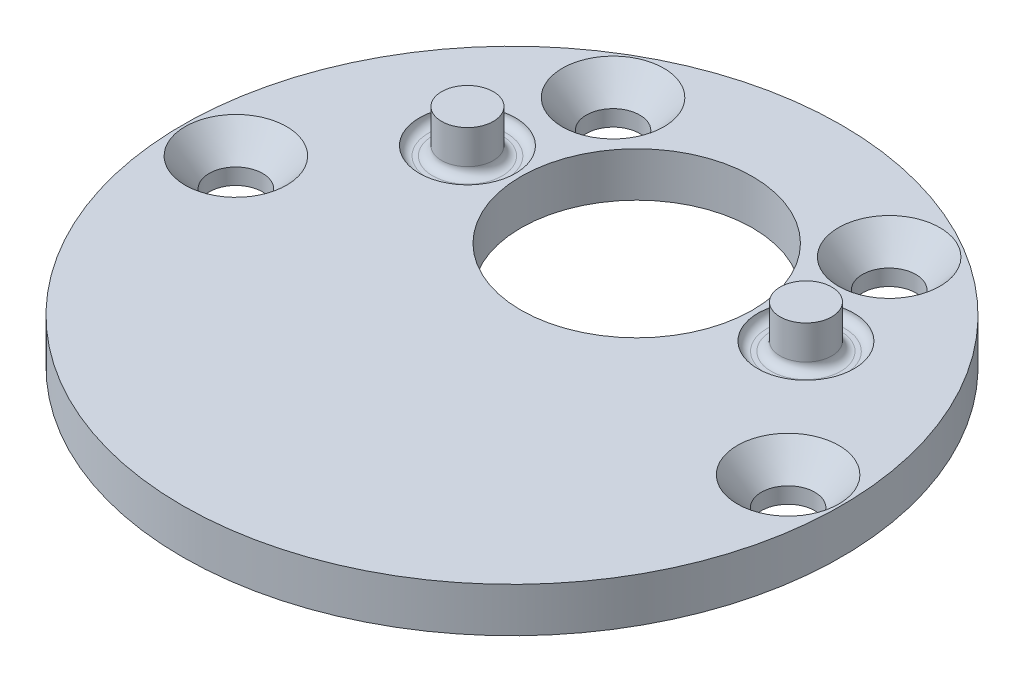
SolidWorks part; units mm, degrees
ref_plane "Front Plane" through (0, 0, 0) normal (0, 0, 1) x (1, 0, 0)
ref_plane "Top Plane" through (0, 0, 0) normal (0, 1, 0) x (1, 0, 0)
ref_plane "Right Plane" through (0, 0, 0) normal (1, 0, 0) x (0, 0, -1)
sketch "Sketch1" plane through (0, 0, 0) normal (0, 1, 0) x (1, 0, 0)
  line L4 (0, 0) -> (15.8817, 0) construction
  line L5 (0, 0) -> (0, 17.0912) construction
  line L6 (-7.75, 13.4234) -> (0, 0) construction
  line L7 (0, 0) -> (7.75, 13.4234) construction
  circle A0 centre (0, 0) radius 15.5 construction
  circle A1 centre (-7.75, 13.4234) radius 1.5
  circle A3 centre (-15.5, 0) radius 1.5
  circle A4 centre (7.75, 13.4234) radius 1.5
  circle A5 centre (15.5, 0) radius 1.5
  circle A6 centre (0, 0) radius 18.5
  dimension "D1" = 31
  dimension "D2" = 3
  dimension "D4" = 37
  dimension "D3" = 60
extrude "Boss-Extrude1" add sketch "Sketch1" along normal blind 2.5
sketch "Sketch2" plane through (0, 2.5, 0) normal (0, 1, 0) x (1, 0, 0)
  line L0 (0, 0) -> (0, 16.6144) construction
  line L1 (0, 0) -> (25.2906, 0) construction
  line L2 (-9.5, 7) -> (9.5, 7) construction
  circle A0 centre (-9.5, 7) radius 1.45
  circle A1 centre (9.5, 7) radius 1.45
  point P8 (0, 8.3072)
  point P11 (0, 7)
  dimension "D3" = 2.9
  dimension "D1" = 7
  dimension "D2" = 19
extrude "Boss-Extrude2" add sketch "Sketch2" along normal blind 1.9 and the other way blind 1
sketch "Sketch6" plane through (0, 2.5, 0) normal (0, 1, 0) x (1, 0, 0)
  line L0 (9.5, 7) -> (-9.5, 7) construction
  line L1 (0, 0) -> (0, 7) construction
  circle A0 centre (-9.5, 7) radius 2.7
  circle A1 centre (9.5, 7) radius 2.7
  circle A2 centre (-9.5, 7) radius 1.45 construction
  circle A3 centre (9.5, 7) radius 1.45
  circle A4 centre (-9.5, 7) radius 1.45
  circle A5 centre (9.5, 7) radius 1.45 construction
  dimension "D1" = 1.25
extrude "Cut-Extrude3" cut sketch "Sketch6" against normal blind 0.5
sketch "Sketch4" plane through (0, 2.5, 0) normal (0, 1, 0) x (1, 0, 0)
  line L0 (9.5, 7) -> (-9.5, 7) construction
  circle A0 centre (0, 7) radius 6.5
  dimension "D1" = 13
extrude "Cut-Extrude1" cut sketch "Sketch4" against normal through all
chamfer "Chamfer1" distance 1.35 distance2 1.6 4 edges at (-15.5, 2.5, 1.5) (15.5, 2.5, 1.5) (7.75, 2.5, -11.9234) (-7.75, 2.5, -11.9234) first distance on face at (0, 2.5, -0.5)
fillet "Fillet1" radius 0.5 4 edges at (9.5, 2, -4.3) (9.5, 2, -5.55) (-9.5, 2, -4.3) (-9.5, 2, -5.55)
move or copy body "Body-Convert to Mesh Body1" [suppressed] bodies to move or copy 104 copy no translate (0, 0, 0)
